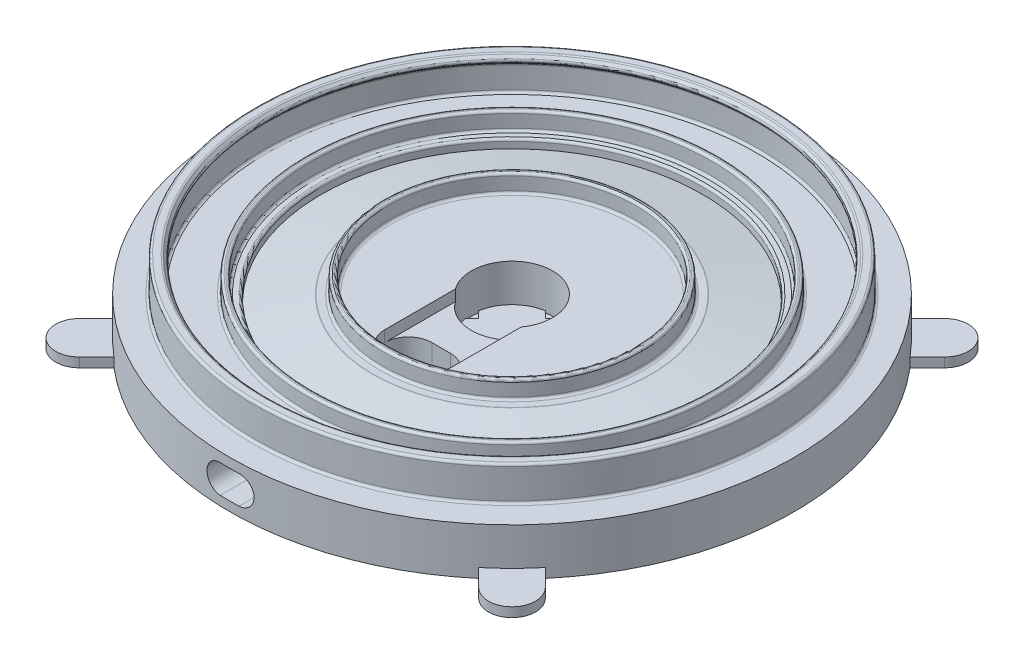
SolidWorks part; units mm, degrees
ref_plane "Front Plane" through (0, 0, 0) normal (0, 0, 1) x (1, 0, 0)
ref_plane "Top Plane" through (0, 0, 0) normal (0, 1, 0) x (1, 0, 0)
ref_plane "Right Plane" through (0, 0, 0) normal (1, 0, 0) x (0, 0, -1)
sketch "Sketch1" plane through (0, 0, 0) normal (0, 1, 0) x (1, 0, 0)
  circle A0 centre (0, 0) radius 60
  circle A1 centre (0, 0) radius 40
  circle A2 centre (0, 0) radius 30
  dimension "D1" = 60
  dimension "D2" = 80
  dimension "D3" = 120
extrude "Boss-Extrude1" add sketch "Sketch1" along normal blind 10 contours A0
sketch "Sketch2" plane through (0, 0, 0) normal (0, 0, 1) x (1, 0, 0)
  line L0 (0, 10) -> (-29.5, 10)
  line L1 (60, 10) -> (-60, 10) construction
  line L2 (-29.5, 10) -> (-40.5, 8.127)
  line L3 (-40.5, 8.127) -> (-40.5, 10)
  line L4 (-40.5, 10) -> (-29.5, 10)
  line L5 (0, 10) -> (0, 0) construction
  dimension "D1" = 11
  dimension "D2" = 29.5
  dimension "D3" = 1.873
revolve "Cut-Revolve1" cut sketch "Sketch2" angle 360 about L5
sketch "Sketch3" plane through (0, 10, 0) normal (0, 1, 0) x (1, 0, 0)
  circle A0 centre (0, 0) radius 27.5
  circle A1 centre (0, 0) radius 26.25
  circle A2 centre (0, 0) radius 42.5
  circle A3 centre (0, 0) radius 43.75
  dimension "D1" = 55
  dimension "D2" = 52.5
  dimension "D3" = 85
  dimension "D4" = 87.5
extrude "Boss-Extrude2" add sketch "Sketch3" along normal blind 3.723 contours A1 | A0 | A2 | A3
fillet "Fillet1" radius 0.5 10 edges at (0, 10, 26.25) (0, 10, 27.5) (0, 10, 43.75) (0, 10, 42.5) (0, 10, 40.5) (0, 13.723, 27.5) (0, 13.723, 26.25) (0, 13.723, 43.75) (0, 13.723, 42.5) (0, 10, 29.5)
sketch "Sketch5" plane through (0, 0, 0) normal (0, 0, 1) x (1, 0, 0)
  line L0 (0, 10) -> (-52.5, 10) construction
  line L1 (60, 10) -> (-60, 10) construction
  line L2 (-52.5, 10) -> (-54.5, 10)
  line L3 (-54.5, 10) -> (-54.5, 17.323)
  line L4 (-54.5, 17.323) -> (-52.5, 17.323)
  line L5 (-52.5, 17.323) -> (-51.5, 16.323)
  line L6 (-51.5, 16.323) -> (-52.5, 15.323)
  line L7 (-52.5, 15.323) -> (-52.5, 10)
  line L8 (0, 10) -> (0, 24.5479) construction
  line L9 (0, -7.5476) -> (0, 7.5476) construction
  dimension "D1" = 52.5
  dimension "D2" = 7.323
  dimension "D3" = 1
  dimension "D4" = 1
  dimension "D5" = 2
  dimension "D6" = 2
revolve "Revolve1" add sketch "Sketch5" angle 360 about L8
fillet "Fillet2" radius 0.5 6 edges at (0, 10, -52.5) (0, 15.323, -52.5) (0, 17.323, -52.5) (0, 16.323, -51.5) (0, 10, -54.5) (0, 17.323, -54.5)
sketch "Sketch6" plane through (0, 10, 0) normal (0, 1, 0) x (1, 0, 0)
  circle A0 centre (0, 0) radius 8.625
  dimension "D1" = 17.25
extrude "Cut-Extrude1" cut sketch "Sketch6" against normal blind 8.354
sketch "Sketch9" plane through (0, 10, 0) normal (0, 1, 0) x (1, 0, 0)
  line L1 (-7, -5.0389) -> (7, -5.0389)
  line L2 (-7, -5.0389) -> (-7, -20.0389)
  line L3 (-7, -20.0389) -> (7, -20.0389)
  line L4 (7, -5.0389) -> (7, -20.0389)
  circle A0 centre (0, 0) radius 8.625 construction
  circle A1 centre (0, 0) radius 8.625 construction
  dimension "D1" = 15
  dimension "D2" = 14
extrude "Cut-Extrude2" cut sketch "Sketch9" against normal blind 2.354
sketch "Sketch10" plane through (0, 10, 0) normal (0, 1, 0) x (1, 0, 0)
  line L0 (2, -20.0389) -> (-2, -20.0389) construction
  line L1 (-7, -20.0389) -> (7, -20.0389) construction
  line L2 (2, -25.0389) -> (-2, -25.0389)
  line L3 (2, -15.0389) -> (-2, -15.0389)
  arc A0 (2, -25.0389) -> (2, -15.0389) centre (2, -20.0389) ccw
  arc A1 (-2, -15.0389) -> (-2, -25.0389) centre (-2, -20.0389) ccw
  point P4 (0, -20.0389)
  dimension "D1" = 5
extrude "Cut-Extrude3" cut sketch "Sketch10" against normal blind 10
sketch "Sketch11" plane through (0, 0, 25.0389) normal (0, 0, -1) x (-1, 0, 0)
  line L0 (-2, 5) -> (2, 5) construction
  line L1 (-2, 8) -> (2, 8)
  line L2 (-2, 2) -> (2, 2)
  line L3 (2, 0) -> (2, 10) construction
  line L4 (-2, 0) -> (-2, 10) construction
  line L5 (2, 0) -> (-2, 0) construction
  arc A0 (-2, 8) -> (-2, 2) centre (-2, 5) ccw
  arc A1 (2, 2) -> (2, 8) centre (2, 5) ccw
  point P2 (0, 5)
  dimension "D1" = 3
  dimension "D2" = 2
extrude "Cut-Extrude4" cut sketch "Sketch11" against normal blind 40 and the other way blind 2
sketch "Sketch12" plane through (0, 0, 0) normal (0, -1, 0) x (1, 0, 0)
  line L0 (-45.9619, -45.9619) -> (45.9619, 45.9619) construction
  line L1 (-49.4975, -42.4264) -> (42.4264, 49.4975)
  line L2 (-42.4264, -49.4975) -> (49.4975, 42.4264)
  line L3 (9.5276, 0) -> (-9.5276, 0) construction
  line L4 (45.9619, -45.9619) -> (-45.9619, 45.9619) construction
  line L5 (42.4264, -49.4975) -> (-49.4975, 42.4264)
  line L6 (49.4975, -42.4264) -> (-42.4264, 49.4975)
  line L7 (0, -9.5276) -> (0, 9.5276) construction
  arc A0 (-49.4975, -42.4264) -> (-42.4264, -49.4975) centre (-45.9619, -45.9619) ccw
  arc A1 (49.4975, 42.4264) -> (42.4264, 49.4975) centre (45.9619, 45.9619) ccw
  circle A2 centre (0, 0) radius 60 construction
  arc A3 (42.4264, -49.4975) -> (49.4975, -42.4264) centre (45.9619, -45.9619) ccw
  arc A4 (-42.4264, 49.4975) -> (-49.4975, 42.4264) centre (-45.9619, 45.9619) ccw
  point P2 (0, 0)
  point P14 (0, 0)
  dimension "D2" = 5
  dimension "D4" = 5
  dimension "D1" = 65
  dimension "D3" = 45
  dimension "D5" = 65
  dimension "D6" = 45
extrude "Boss-Extrude3" add sketch "Sketch12" against normal blind 2 contours L6 A4 L5 A3 | L2 A1 L1 A0
